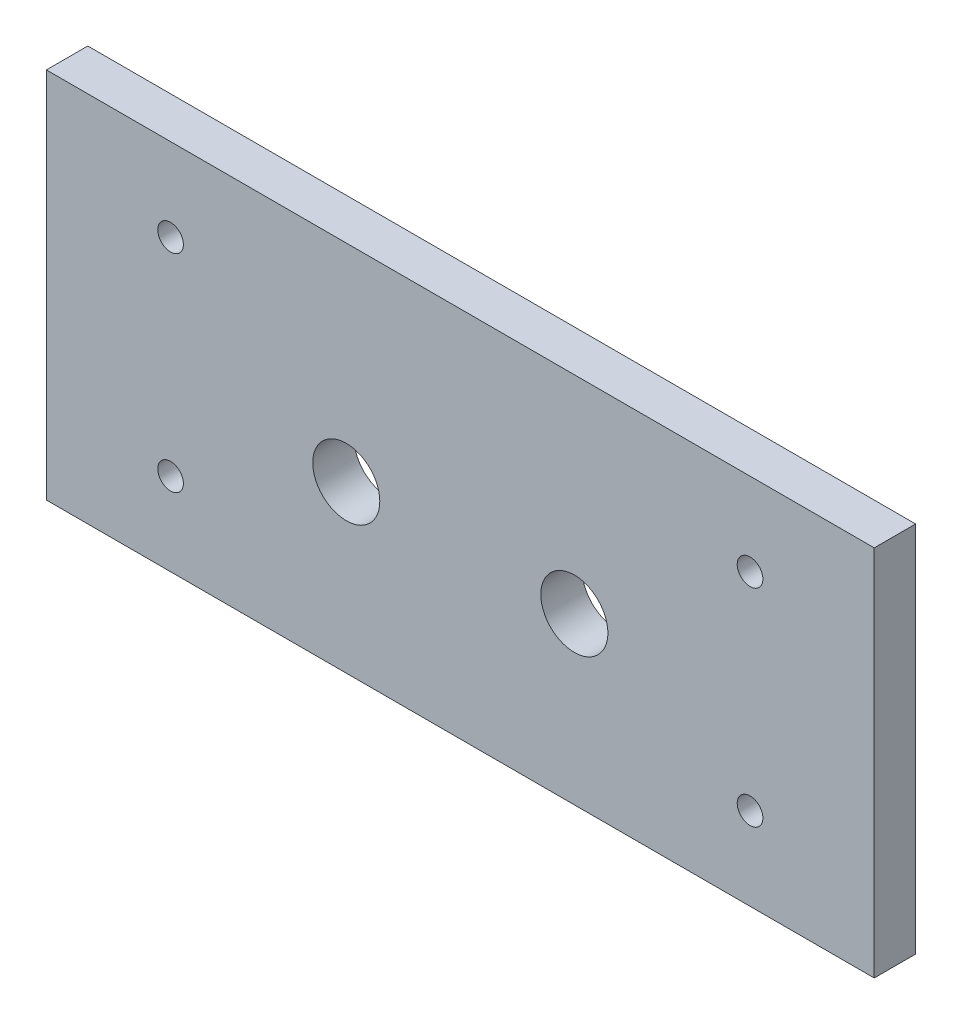
SolidWorks part; units mm, degrees
ref_plane "Plan de face" through (0, 0, 0) normal (0, 0, 1) x (1, 0, 0)
ref_plane "Plan de dessus" through (0, 0, 0) normal (0, 1, 0) x (1, 0, 0)
ref_plane "Plan de droite" through (0, 0, 0) normal (1, 0, 0) x (0, 0, -1)
sketch "Esquisse1" plane through (0, 0, 0) normal (0, 0, 1) x (1, 0, 0)
  line L0 (0, 0) -> (0, 16.8216) construction
  line L1 (-50, -22.5) -> (50, -22.5)
  line L2 (-50, -22.5) -> (-50, 22.5)
  line L3 (-50, 22.5) -> (50, 22.5)
  line L4 (50, -22.5) -> (50, 22.5)
  line L5 (-50, -22.5) -> (50, 22.5) construction
  line L6 (-50, 22.5) -> (50, -22.5) construction
  line L7 (0, 0) -> (42.1574, 0) construction
  circle A0 centre (-35, -12.5) radius 1.55
  circle A1 centre (-35, 12.5) radius 1.55
  circle A2 centre (35, -12.5) radius 1.55
  circle A3 centre (35, 12.5) radius 1.55
  circle A5 centre (-13.775, -2.5) radius 4.05
  circle A6 centre (13.775, -2.5) radius 4.05
  point P0 (0, 0)
  dimension "D3" = 3.1
  dimension "D7" = 8.1
  dimension "D1" = 100
  dimension "D2" = 45
  dimension "D4" = 15
  dimension "D5" = 10
  dimension "D9" = 14
  dimension "D10" = 25
extrude "Boss.-Extru.1" add sketch "Esquisse1" against normal blind 5
